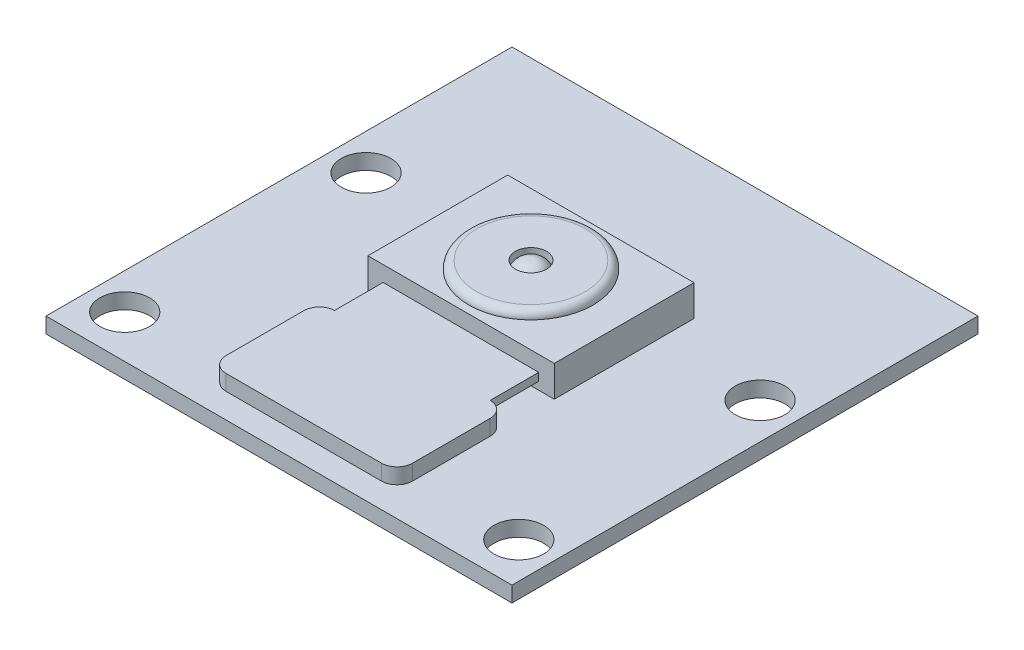
SolidWorks part; units mm, degrees
ref_plane "Alzado" through (0, 0, 0) normal (0, 0, 1) x (1, 0, 0)
ref_plane "Planta" through (0, 0, 0) normal (0, 1, 0) x (1, 0, 0)
ref_plane "Vista lateral" through (0, 0, 0) normal (1, 0, 0) x (0, 0, -1)
sketch "Croquis1" plane through (0, 0, 0) normal (0, 1, 0) x (1, 0, 0)
  line L0 (0, 10.1956) -> (0, -15.9876) construction
  line L1 (-15, -15) -> (15, -15)
  line L2 (-15, -15) -> (-15, 15)
  line L3 (-15, 15) -> (15, 15)
  line L4 (15, -15) -> (15, 15)
  line L5 (-15, -15) -> (15, 15) construction
  line L6 (-15, 15) -> (15, -15) construction
  line L7 (0, -55) -> (0, 55) construction
  circle A0 centre (-12.6844, 3.2861) radius 1.6
  circle A1 centre (-12.6844, -12.2471) radius 1.6
  circle A2 centre (12.6844, -12.2471) radius 1.6
  circle A3 centre (12.6844, 3.2861) radius 1.6
  point P0 (0, 0)
extrude "Saliente-Extruir1" add sketch "Croquis1" along normal blind 1
sketch "Croquis2" plane through (0, 1, 0) normal (0, 1, 0) x (1, 0, 0)
  line L0 (0, -0.55) -> (0, 0.55) construction
  line L1 (-5, -13.4035) -> (5, -13.4035)
  line L2 (-6, -12.4035) -> (-6, -7.4035)
  line L3 (-5, -6.4035) -> (5, -6.4035)
  line L4 (6, -12.4035) -> (6, -7.4035)
  line L5 (-6, -13.4035) -> (6, -6.4035) construction
  line L6 (-6, -6.4035) -> (6, -13.4035) construction
  arc A0 (5, -13.4035) -> (6, -12.4035) centre (5, -12.4035) ccw
  arc A1 (5, -6.4035) -> (6, -7.4035) centre (5, -7.4035) cw
  arc A2 (-5, -13.4035) -> (-6, -12.4035) centre (-5, -12.4035) cw
  arc A3 (-6, -7.4035) -> (-5, -6.4035) centre (-5, -7.4035) cw
  point P0 (0, -9.9035)
  dimension "D1" = 1
extrude "Saliente-Extruir2" add sketch "Croquis2" along normal blind 1
sketch "Croquis3" plane through (0, 1, 0) normal (0, 1, 0) x (1, 0, 0)
  line L0 (0, -1.1) -> (0, 1.1) construction
  line L1 (-6, -3.2785) -> (6, -3.2785)
  line L2 (-6, -3.2785) -> (-6, 5.7215)
  line L3 (-6, 5.7215) -> (6, 5.7215)
  line L4 (6, -3.2785) -> (6, 5.7215)
  line L5 (-6, -3.2785) -> (6, 5.7215) construction
  line L6 (-6, 5.7215) -> (6, -3.2785) construction
  point P0 (0, 1.2215)
extrude "Saliente-Extruir3" add sketch "Croquis3" along normal blind 2
sketch "Croquis4" plane through (0, 0, 6.4035) normal (0, 0, -1) x (-1, 0, 0)
  line L0 (-5, 2) -> (-5, 1.5)
  line L1 (-5, 2) -> (5.0224, 2)
  line L2 (-5, 1.5) -> (5.0224, 1.5)
  line L3 (5.0224, 2) -> (5.0224, 1.5)
  line L4 (-5, 2) -> (-5, 1) construction
extrude "Saliente-Extruir4" add sketch "Croquis4" along normal blind 4
sketch "Croquis6" plane through (0, 3, 0) normal (0, 1, 0) x (1, 0, 0)
  line L0 (-6, 1.2215) -> (6, 1.2215) construction
  line L1 (-6, 5.7215) -> (-6, -3.2785) construction
  line L2 (6, -3.2785) -> (6, 5.7215) construction
  circle A0 centre (0, 1.2215) radius 4
extrude "Saliente-Extruir5" add sketch "Croquis6" along normal blind 0.5
fillet "Redondeo1" radius 0.5 1 edges at (0, 3.5, 2.7785)
sketch "Croquis7" plane through (0, 3.5, 0) normal (0, 1, 0) x (1, 0, 0)
  circle A0 centre (0, 1.2215) radius 1
extrude "Cortar-Extruir1" cut sketch "Croquis7" against normal blind 0.5
sketch "Croquis9" plane through (0, 0, 0) normal (1, 0, 0) x (0, 0, -1)
  line L0 (0.2195, 2.9972) -> (1.217, 2.9972) construction
  line L1 (1.217, 2.9972) -> (1.217, 3.5463) construction
  line L2 (0.2195, 2.9972) -> (1.217, 2.9972)
  line L3 (1.217, 2.9972) -> (1.217, 3.5463)
  line L4 (1.217, 2.9972) -> (1.217, 3.9896) construction
  arc A0 (0.2195, 2.9972) -> (1.217, 3.5463) centre (1.0839, 2.6074) cw
revolve "Revolución1" add sketch "Croquis9" angle 360 about L4
